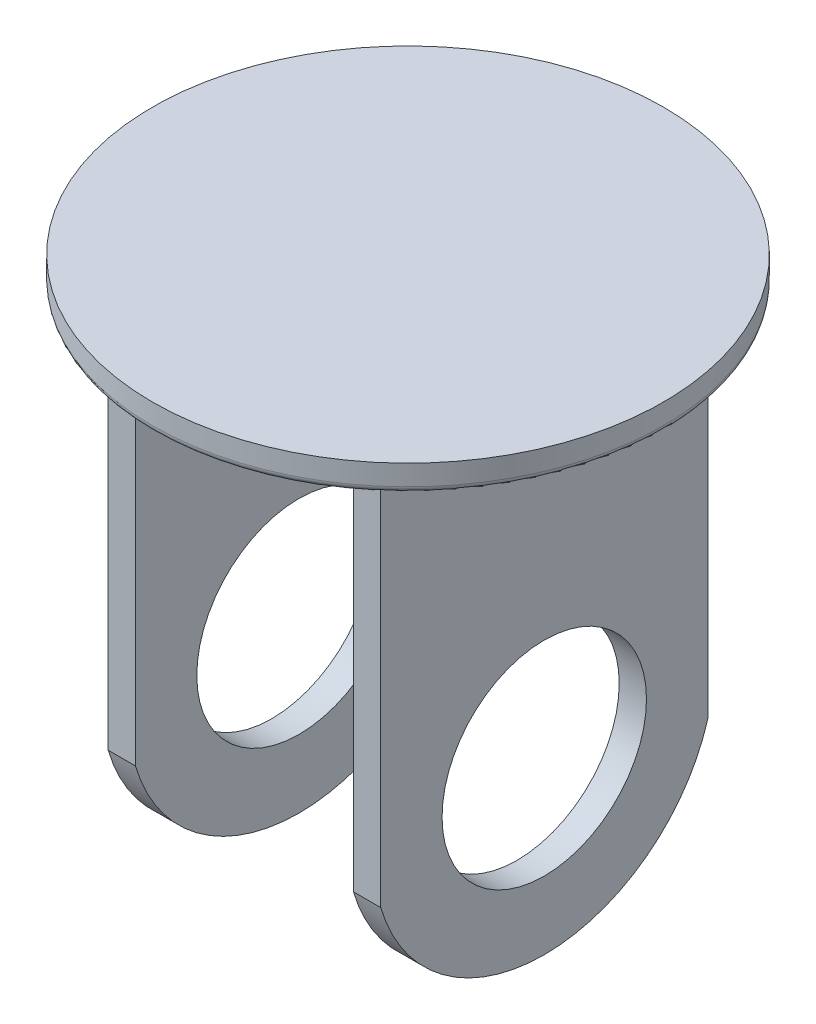
SolidWorks part; units mm, degrees
material "6061 合金"
ref_plane "前视基准面" through (0, 0, 0) normal (0, 0, 1) x (1, 0, 0)
ref_plane "上视基准面" through (0, 0, 0) normal (0, 1, 0) x (1, 0, 0)
ref_plane "右视基准面" through (0, 0, 0) normal (1, 0, 0) x (0, 0, -1)
other "Configuration Table"
sketch "草图1" plane through (0, 0, 0) normal (0, 0, 1) x (1, 0, 0)
  line L0 (0, 0) -> (0, 107.8742) construction
  line L1 (-40, 158) -> (40, 158)
  line L2 (40, 158) -> (40, 0)
  line L3 (40, 0) -> (32, 0)
  line L4 (32, 0) -> (32, 150)
  line L5 (32, 150) -> (-32, 150)
  line L6 (-32, 0) -> (-32, 150)
  line L7 (-40, 0) -> (-32, 0)
  line L8 (-40, 158) -> (-40, 0)
  point P10 (0, 150)
  point P13 (0, 158)
  dimension "D1" = 8
  dimension "D2" = 8
  dimension "D3" = 150
  dimension "D4" = 40
extrude "凸台-拉伸1" add sketch "草图1" along normal blind 96
sketch "草图2" plane through (40, 0, 0) normal (1, 0, 0) x (0, 0, -1)
  line L0 (-123.2261, 50) -> (13.6686, 50) construction
  line L1 (-48, 160.6634) -> (-48, -4.975) construction
  line L2 (0, 0) -> (0, 158) construction
  line L3 (-96, 0) -> (-96, 158) construction
  line L4 (-96, 150) -> (0, 150) construction
  line L5 (-96, 158) -> (0, 158) construction
  line L6 (-96, 0) -> (0, 0) construction
  line L8 (-96, 0) -> (0, 0)
  line L9 (-96, 0) -> (-96, 36)
  line L10 (0, 0) -> (0, 36)
  circle A0 centre (-48, 50) radius 30
  arc A1 (-96, 36) -> (0, 36) centre (-48, 50) ccw
  line M5 (0, 0) -> (0, 158)
  line M7 (-96, 158) -> (-96, 0)
  line M8 (-96, 0) -> (0, 0)
  dimension "D2" = 60
  dimension "D1" = 8
  dimension "D3" = 50
extrude "切除-拉伸1" cut sketch "草图2" against normal blind 172 contours A1 M7 M8 | A1 L8 M5 | A0 region at (40, 9.5121, 85.0085) region at (40, 9.5121, 10.9915) region at (40, 50, 48)
sketch "草图3" plane through (0, 158, 0) normal (0, 1, 0) x (1, 0, 0)
  line L0 (-96.0997, -48) -> (89.2664, -48) construction
  line L1 (0, 0) -> (0, -103.4147) construction
  line L2 (40, 0) -> (-40, 0) construction
  line L3 (40, -96) -> (-40, -96) construction
  circle A0 centre (0, -48) radius 75
  dimension "D1" = 150
extrude "凸台-拉伸2" add sketch "草图3" against normal up to surface (8 mm away) up to face at (0, 150, 48)
ref_plane "基准面1" through (0, 0, 48) normal (0, 0, -1) x (-1, 0, 0)
sketch "草图4" plane through (0, 0, 48) normal (0, 0, -1) x (-1, 0, 0)
  line L0 (-75, 150) -> (75, 150) construction
  line L1 (-40, 36) -> (-40, 150) construction
  line L2 (40, 150) -> (40, 36) construction
  line L3 (-75, 150) -> (-40, 150) construction
  line L4 (-40, 90) -> (-40, 150) construction
  line L5 (40, 150) -> (40, 90) construction
  line L6 (75, 150) -> (40, 90) construction
  line L7 (-75, 150) -> (-40, 90) construction
  line L8 (40, 150) -> (75, 150) construction
  line L9 (32, 90) -> (2, 150)
  line L10 (32, 36) -> (32, 150) construction
  line L11 (-32, 90) -> (-2, 150)
  line L12 (-32, 150) -> (-32, 36) construction
  line L13 (-2, 150) -> (-32, 150)
  line L14 (-32, 150) -> (-32, 90)
  line L15 (2, 150) -> (32, 150)
  line L16 (32, 150) -> (32, 90)
  dimension "D1" = 60
  dimension "D2" = 60
  dimension "D3" = 30
  dimension "D4" = 30
extrude "凸台-拉伸3" add sketch "草图4" along normal mid plane 10
fillet "圆角1" radius 2 22 edges at (-2, 150, 48) (-32, 90, 48) (32, 90, 48) (2, 150, 48) (-17, 150, 53) (-17, 120, 53) (-32, 120, 53) (-17, 120, 43) (-17, 150, 43) (-32, 120, 43) (17, 150, 43) (17, 120, 43) (32, 120, 43) (17, 120, 53) (17, 150, 53) (32, 120, 53) (32, 150, 21.5) (36, 150, 0) (40, 150, 48) (36, 150, 96) (32, 150, 74.5) (0, 150, 123)
